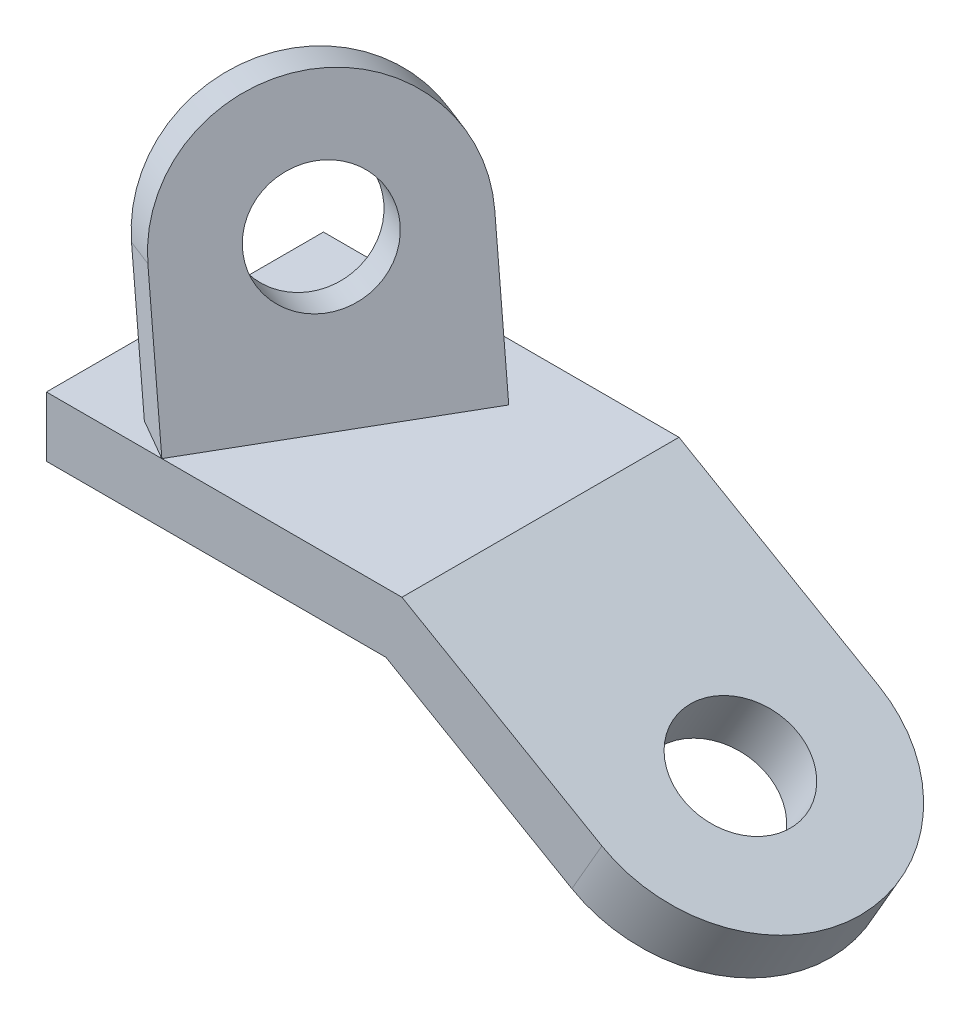
SolidWorks part; units mm, degrees
ref_plane "Front Plane" through (0, 0, 0) normal (0, 0, 1) x (1, 0, 0)
ref_plane "Top Plane" through (0, 0, 0) normal (0, 1, 0) x (1, 0, 0)
ref_plane "Right Plane" through (0, 0, 0) normal (1, 0, 0) x (0, 0, -1)
sketch "Sketch1" plane through (0, 0, 0) normal (0, 0, 1) x (1, 0, 0)
  line L0 (0, 0) -> (0, 13)
  line L1 (0, 13) -> (77, 13)
  line L2 (77, 13) -> (120.3013, -12)
  line L3 (120.3013, -12) -> (113.8013, -23.2583)
  line L4 (113.8013, -23.2583) -> (73.5167, 0)
  line L5 (73.5167, 0) -> (0, 0)
  point P7 (0, 0)
  point P8 (77, -2.0177)
  point P9 (-80.0149, 10.2454)
  dimension "D1" = 150
  dimension "D2" = 13
  dimension "D3" = 13
  dimension "D4" = 77
  dimension "D6" = 50
  dimension "D7" = 90
  dimension "D8" = 90
extrude "Boss-Extrude1" add sketch "Sketch1" against normal blind 60
sketch "Sketch2" plane through (24.8792, 43.092, 0) normal (0.5, 0.866, 0) x (0.866, -0.5, 0)
  line L1 (110.184, 60) -> (110.184, 0)
  arc A1 (110.184, 60) -> (110.184, 0) centre (110.184, 30) cw
  circle A2 centre (110.184, 30) radius 12.5
  line M2 (110.184, 0) -> (110.184, 60)
  dimension "D1" = 25
  dimension "D2" = 30
extrude "Boss-Extrude2" add sketch "Sketch2" against normal blind 13 contours A2 A1 M2 region at (132.6791, -19.1464, -30)
extrude "Cut-Extrude1" cut sketch "Sketch2<3>" against normal blind 13 contours L1 A2 region at (115.7069, -9.3474, -30)
sketch "Sketch2<3>" plane through (24.8792, 43.092, 0) normal (0.5, 0.866, 0) x (0.866, -0.5, 0) same geometry as "Sketch2"
sketch "Sketch6" plane through (0, 13, 0) normal (0, 1, 0) x (1, 0, 0)
  line L0 (25, 0) -> (46.8049, 37.7672)
  line L1 (77, 0) -> (0, 0) construction
  dimension "D1" = 60
  dimension "D2" = 25
ref_plane "Plane3" through (20.3086, 6.2835, 11.7252) normal (0.8365, 0.2588, 0.483) x (0.5, 0, -0.866)
sketch "Sketch7" plane through (20.3086, 6.2835, 11.7252) normal (0.8365, 0.2588, 0.483) x (0.5, 0, -0.866)
  line L0 (12.5, 6.9534) -> (67.5, 6.9534)
  line L2 (12.5, 6.9534) -> (12.5, 38.9534)
  line L4 (12.5, 38.9534) -> (67.5, 38.9534)
  line L5 (67.5, 38.9534) -> (67.5, 6.9534)
  arc A1 (12.5, 38.9534) -> (67.5, 38.9534) centre (40, 38.9534) cw
  circle A2 centre (40, 38.9534) radius 12.5
  dimension "D3" = 25
  dimension "D4" = 27.5
  dimension "D1" = 55
  dimension "D2" = 32
extrude "Boss-Extrude5" add sketch "Sketch7" against normal blind 10 contours A2 L4 L2 L0 L5 | A2 L4 A1 region at (35.5522, 26.7808, -25.662) region at (28.5897, 56.7847, -29.6817)
